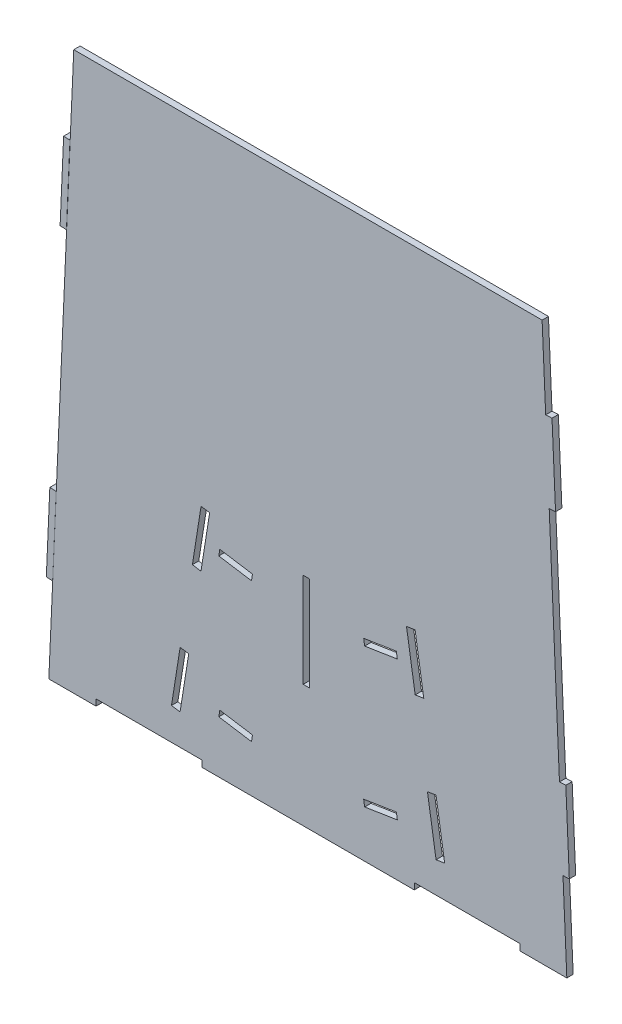
SolidWorks part; units mm, degrees
ref_plane "Front Plane" through (0, 0, 0) normal (0, 0, 1) x (1, 0, 0)
ref_plane "Top Plane" through (0, 0, 0) normal (0, 1, 0) x (1, 0, 0)
ref_plane "Right Plane" through (0, 0, 0) normal (1, 0, 0) x (0, 0, -1)
sketch "Sketch1" plane through (0, 0, 0) normal (0, 0, 1) x (1, 0, 0)
  line L0 (-62.1053, -13.2698) -> (-56.1208, 120.4303)
  line L1 (-56.1208, 120.4303) -> (56.213, 120.4303)
  line L2 (56.213, 120.4303) -> (62.1421, -13.2698)
  line L3 (62.1421, -13.2698) -> (-62.1053, -13.2698)
  line L4 (0.0184, -13.2698) -> (0.0184, -120.4303) construction
extrude "Boss-Extrude1" add sketch "Sketch1" along normal blind 1.524 contours L3 L2 L1 L0 region at (0.032, 52.4581, 0)
sketch "Sketch2" plane through (0, 0, 1.524) normal (0, 0, 1) x (1, 0, 0)
  line L5 (0.0184, 111.4688) -> (0.0184, 198.9405) construction
  line L11 (-62.7047, 7.6127) -> (-61.8607, 26.644)
  line L14 (57.9108, 82.1443) -> (59.4333, 82.2119)
  line L15 (57.0668, 101.1756) -> (58.5893, 101.2431)
  line L16 (57.9108, 82.1443) -> (57.0668, 101.1756)
  line L17 (59.4333, 82.2119) -> (58.5893, 101.2431)
  line L19 (61.219, 7.5452) -> (62.7415, 7.6127)
  line L20 (60.375, 26.5765) -> (61.8975, 26.644)
  line L21 (61.219, 7.5452) -> (60.375, 26.5765)
  line L22 (62.7415, 7.6127) -> (61.8975, 26.644)
  line L23 (-61.1822, 7.5452) -> (-60.3382, 26.5765)
  line L24 (-60.3382, 26.5765) -> (-61.8607, 26.644)
  line L25 (-61.1822, 7.5452) -> (-62.7047, 7.6127)
  line L26 (-59.3965, 82.2119) -> (-58.5525, 101.2431)
  line L27 (-57.874, 82.1443) -> (-57.03, 101.1756)
  line L28 (-57.03, 101.1756) -> (-58.5525, 101.2431)
  line L29 (-57.874, 82.1443) -> (-59.3965, 82.2119)
extrude "Boss-Extrude2" add sketch "Sketch2" against normal blind 1.524
sketch "Sketch6" plane through (0, 0, 1.524) normal (0, 0, 1) x (1, 0, 0)
  line L1 (25.5473, -11.7458) -> (50.9473, -11.7458)
  line L2 (25.5473, -11.7458) -> (25.5473, -13.2698)
  line L3 (25.5473, -13.2698) -> (50.9473, -13.2698)
  line L4 (50.9473, -11.7458) -> (50.9473, -13.2698)
  line L5 (-50.791, -11.7458) -> (-25.391, -11.7458)
  line L6 (-50.791, -11.7458) -> (-50.791, -13.2698)
  line L7 (-50.791, -13.2698) -> (-25.391, -13.2698)
  line L8 (-25.391, -11.7458) -> (-25.391, -13.2698)
extrude "Cut-Extrude3" cut sketch "Sketch6" against normal blind 1.524
sketch "Sketch7" plane through (0, 0, 0) normal (0, 0, -1) x (-1, 0, 0)
  line L0 (25.5871, 40.8591) -> (27.6681, 27.6782)
  line L1 (23.6959, 52.8381) -> (33.8922, -11.7458) construction
  line L2 (30.61, 9.0441) -> (32.6789, -4.0608)
  line L3 (28.554, 8.7195) -> (30.6229, -4.3854)
  line L4 (23.5311, 40.5345) -> (25.6121, 27.3536)
  line L5 (32.6789, -4.0608) -> (30.6229, -4.3854)
  line L6 (28.554, 8.7195) -> (30.61, 9.0441)
  line L7 (-21.3709, 33.4141) -> (-13.5306, 32.1763) construction
  line L8 (25.5871, 40.8591) -> (23.5311, 40.5345)
  line L9 (27.6681, 27.6782) -> (25.6121, 27.3536)
  line L10 (-0.0781, 52.8381) -> (-0.0781, 98.3561) construction
  line L11 (-23.8521, 52.8381) -> (23.6959, 52.8381) construction
  line L12 (-30.7662, 9.0441) -> (-32.8351, -4.0608)
  line L13 (-25.7433, 40.8591) -> (-27.8243, 27.6782)
  line L14 (-27.8243, 27.6782) -> (-25.7682, 27.3536)
  line L15 (-25.7433, 40.8591) -> (-23.6873, 40.5345)
  line L16 (-0.4313, 38.77) -> (1.0927, 38.77)
  line L17 (-28.7102, 8.7195) -> (-30.7662, 9.0441)
  line L18 (-32.8351, -4.0608) -> (-30.7791, -4.3854)
  line L19 (-23.6873, 40.5345) -> (-25.7682, 27.3536)
  line L20 (-28.7102, 8.7195) -> (-30.7791, -4.3854)
  line L21 (-0.4313, 38.77) -> (-0.4313, 16.1111)
  line L22 (-0.4313, 16.1111) -> (1.0927, 16.1111)
  line L23 (1.0927, 38.77) -> (1.0927, 16.1111)
  line L24 (-0.4313, 38.77) -> (1.0927, 16.1111) construction
  line L25 (-0.4313, 16.1111) -> (1.0927, 38.77) construction
  line L26 (-21.3709, 0) -> (-13.5306, -1.2378) construction
  line L27 (-21.4898, 32.6614) -> (-13.6494, 31.4236)
  line L28 (-21.4898, -0.7527) -> (-13.6494, -1.9905)
  line L29 (-21.2521, 34.1668) -> (-13.4117, 32.929)
  line L30 (-21.2521, 0.7527) -> (-13.4117, -0.4851)
  line L31 (-21.4898, 32.6614) -> (-21.2521, 34.1668)
  line L32 (-13.6494, 31.4236) -> (-13.4117, 32.929)
  line L33 (-21.4898, -0.7527) -> (-21.2521, 0.7527)
  line L34 (-13.6494, -1.9905) -> (-13.4117, -0.4851)
  line L35 (21.2148, 0) -> (13.3744, -1.2378) construction
  line L36 (21.2148, 33.4141) -> (13.3744, 32.1763) construction
  line L37 (13.4932, -1.9905) -> (13.2555, -0.4851)
  line L38 (21.3336, -0.7527) -> (21.0959, 0.7527)
  line L39 (13.4932, 31.4236) -> (13.2555, 32.929)
  line L40 (21.3336, 32.6614) -> (21.0959, 34.1668)
  line L41 (21.0959, 0.7527) -> (13.2555, -0.4851)
  line L42 (21.0959, 34.1668) -> (13.2555, 32.929)
  line L43 (21.3336, -0.7527) -> (13.4932, -1.9905)
  line L44 (21.3336, 32.6614) -> (13.4932, 31.4236)
  point P20 (0.3307, 27.4406)
  dimension "D1" = 0.762
  dimension "D2" = 0.762
extrude "Cut-Extrude4" cut sketch "Sketch7" against normal blind 1.524
